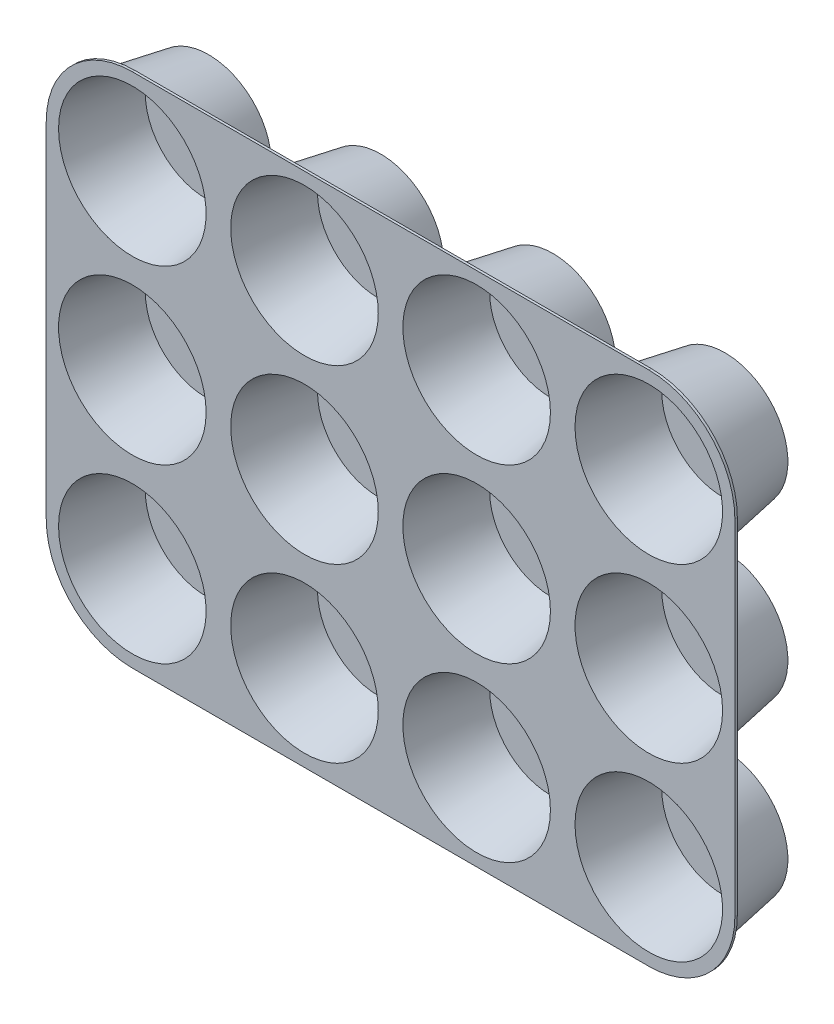
SolidWorks part; units mm, degrees
ref_plane "Front Plane" through (0, 0, 0) normal (1, 0, 0) x (0, 1, 0)
ref_plane "Top Plane" through (0, 0, 0) normal (0, 0, 1) x (0, 1, 0)
ref_plane "Right Plane" through (0, 0, 0) normal (0, 1, 0) x (-1, 0, 0)
sketch "Sketch1" plane through (0, 0, 0) normal (1, 0, 0) x (0, 1, 0)
  line L0 (0, 0) -> (38.1, 0) construction
  line L1 (38.1, 0) -> (31.3819, -38.1)
  line L2 (31.3819, -38.1) -> (0, -38.1)
  line L3 (0, -38.1) -> (0, 0) construction
  line L4 (38.1, 0) -> (44.45, 0)
  line L5 (44.45, 0) -> (44.45, -1.27)
  line L6 (44.45, -1.27) -> (39.1657, -1.27)
  line L7 (39.1657, -1.27) -> (32.4476, -39.37)
  line L8 (32.4476, -39.37) -> (0, -39.37)
  line L9 (0, -39.37) -> (0, -38.1)
  dimension "D1" = 1.27
  dimension "D2" = 38.1
  dimension "D3" = 38.1
  dimension "D4" = 1.27
  dimension "D5" = 1.27
  dimension "D6" = 44.45
  dimension "D7" = 100
revolve "Revolve1" add sketch "Sketch1" angle 360 about L3
ref_axis "Axis1" through (0, 0, 0) along (0, 1, 0)
ref_axis "Axis2" through (0, 0, 0) along (1, 0, 0)
pattern_linear "LPattern1" count 3 spacing 88.9 along (0, -1, 0) count 4 spacing 88.9 along (1, 0, 0) of bodies 101
sketch "Sketch3" plane through (0, 0, 0) normal (0, 0, 1) x (1, 0, 0)
  line L0 (0, -222.25) -> (266.7, -222.25)
  line L1 (-44.45, 0) -> (-44.45, -177.8)
  line L2 (0, 44.45) -> (266.7, 44.45)
  line L3 (311.15, 0) -> (311.15, -177.8)
  circle A0 centre (0, 0) radius 44.45 construction
  circle A1 centre (266.7, -177.8) radius 44.45 construction
  circle A2 centre (0, 0) radius 44.45
  circle A3 centre (266.7, -177.8) radius 44.45
  circle A4 centre (266.7, 0) radius 44.45 construction
  circle A5 centre (0, -177.8) radius 44.45 construction
  circle A6 centre (266.7, 0) radius 44.45
  circle A7 centre (0, -177.8) radius 44.45
  circle A8 centre (0, 0) radius 38.1 construction
  circle A9 centre (0, 0) radius 38.1
  circle A10 centre (177.8, -88.9) radius 38.1 construction
  circle A11 centre (177.8, 0) radius 38.1 construction
  circle A12 centre (0, -88.9) radius 38.1 construction
  circle A13 centre (88.9, -88.9) radius 38.1 construction
  circle A14 centre (88.9, 0) radius 38.1 construction
  circle A15 centre (177.8, -88.9) radius 38.1
  circle A16 centre (177.8, 0) radius 38.1
  circle A17 centre (0, -88.9) radius 38.1
  circle A18 centre (88.9, -88.9) radius 38.1
  circle A19 centre (88.9, 0) radius 38.1
  circle A20 centre (88.9, -177.8) radius 38.1 construction
  circle A21 centre (177.8, -177.8) radius 38.1 construction
  circle A22 centre (266.7, -88.9) radius 38.1 construction
  circle A23 centre (88.9, -177.8) radius 38.1
  circle A24 centre (177.8, -177.8) radius 38.1
  circle A25 centre (266.7, -88.9) radius 38.1
  circle M6 centre (0, 0) radius 44.45
extrude "Boss-Extrude1" add sketch "Sketch3" against normal up to surface (1.27 mm away) contours A7 L0 A3 L3 A6 L2 L1 A25 A24 A23 A19 A18 A17 A16 A15 M6 region at (133.35, -88.9, 0) up to face at (44.45, -177.8, -1.27)
